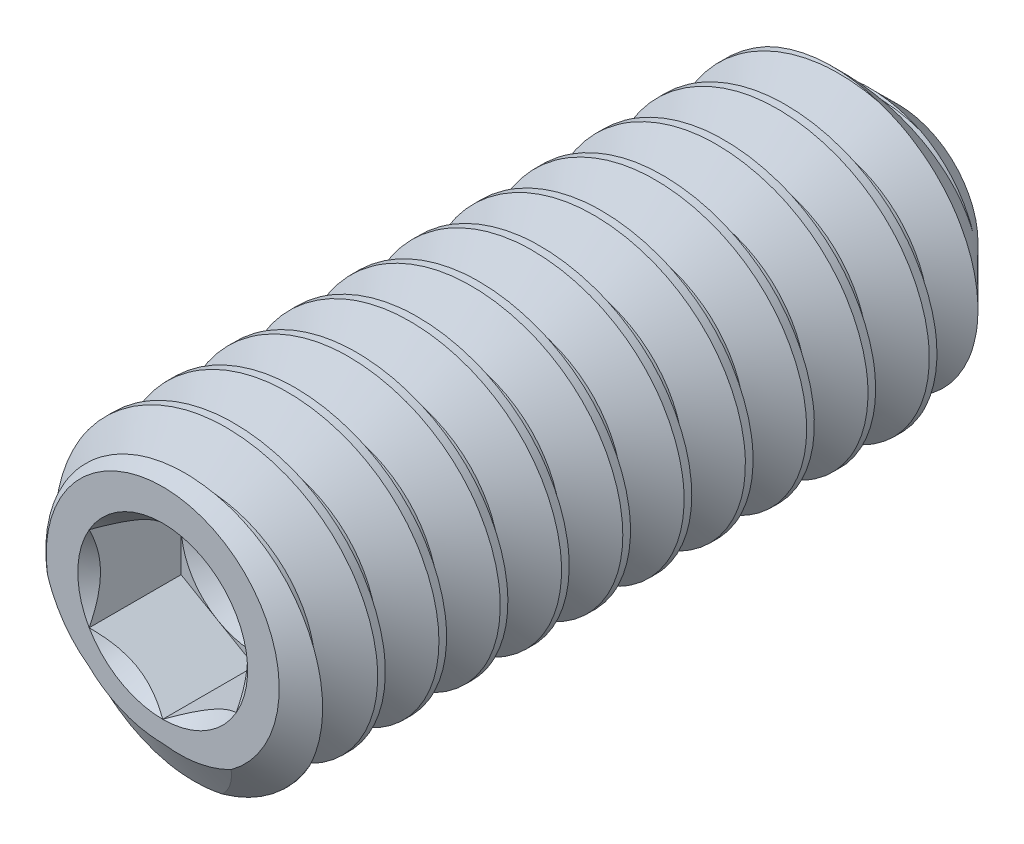
SolidWorks part; units mm, degrees
ref_plane "Front" through (0, 0, 0) normal (0, 0, 1) x (1, 0, 0)
ref_plane "Top" through (0, 0, 0) normal (0, 1, 0) x (1, 0, 0)
ref_plane "Right" through (0, 0, 0) normal (1, 0, 0) x (0, 0, -1)
sketch "Sketch22" plane through (0, 0, 0) normal (1, 0, 0) x (0, 0, -1)
  line L0 (-2.968, 0) -> (-2.968, 1.0058)
  line L1 (-2.968, 1.0058) -> (-2.7919, 1.2573)
  line L2 (-2.7919, 1.2573) -> (2.8136, 1.2573)
  line L3 (2.8136, 1.2573) -> (3.382, 0.689)
  line L4 (3.382, 0.689) -> (2.968, 0)
  line L5 (2.968, 0) -> (-2.968, 0)
  line L6 (2.968, 0) -> (3.382, 0) construction
  line L7 (3.382, 0) -> (3.382, 0.689) construction
  line L8 (3.382, -0.689) -> (2.968, 0) construction
  line L9 (-2.7919, -1.2573) -> (2.8136, -1.2573) construction
  line L10 (3.382, -1.2573) -> (3.382, 1.2573) construction
  line L11 (3.382, 1.2573) -> (2.8528, 1.2573) construction
  point P11 (2.0591, -1.2573)
  point P15 (3.382, 0)
  dimension "D3" = 35
  dimension "D5" = 118
  dimension "D6" = 45
  dimension "D7" = 2.0117
  dimension "D1" = 1.3229
revolve "Revolve1" add sketch "Sketch22" angle 360 about L6
ref_plane "Plane1" through (0, 0, -3.382) normal (0, 0, 1) x (1, 0, 0)
sketch "Sketch27" plane through (0, 0, -3.382) normal (0, 0, 1) x (1, 0, 0)
  circle A0 centre (0, 0) radius 1.2573 construction
  circle A1 centre (0, 0) radius 1.2573
sketch "Sketch23" plane through (0, 0, 2.968) normal (0, 0, 1) x (1, 0, 0)
  line L1 (0, 0.7332) -> (-0.635, 0.3666)
  line L2 (-0.635, 0.3666) -> (-0.635, -0.3666)
  line L3 (-0.635, -0.3666) -> (0, -0.7332)
  line L4 (0, -0.7332) -> (0.635, -0.3666)
  line L5 (0.635, -0.3666) -> (0.635, 0.3666)
  line L6 (0.635, 0.3666) -> (0, 0.7332)
  circle A0 centre (0, 0) radius 0.635 construction
extrude "Cut-Extrude10" cut sketch "Sketch23" against normal blind 0.7937
sketch "Sketch24" plane through (0, 0, 2.968) normal (0, 0, 1) x (1, 0, 0)
  circle A0 centre (0, 0) radius 0.7332
extrude "Cut-Extrude11" cut sketch "Sketch24" against normal through all draft 45
sketch "Sketch26" plane through (0, 0, 2.1743) normal (0, 0, 1) x (1, 0, 0)
  circle A0 centre (0, 0) radius 0.635 construction
  circle A1 centre (0, 0) radius 0.635
extrude "Cut-Extrude12" cut sketch "Sketch26" against normal through all draft 60
sketch "Sketch31" plane through (0, 0, 0) normal (1, 0, 0) x (0, 0, -1)
  line L2 (2.968, 0) -> (3.382, -0.689)
  line L3 (3.382, 0.689) -> (2.968, 0)
ref_axis "Center Axis1" through (0, 0, -42.9554) along (0, 0, 1)
ref_plane "Contact Plane1" through (0, 0, -3.382) normal (0, 0, 1) x (1, 0, 0)
ref_plane "Contact Plane2" through (0, 0, 2.968) normal (0, 0, 1) x (1, 0, 0)
curve "Helix/Spiral1" pitch 0.5292 height 6.8792 radius 1.2573 centre (0, 0, -3.382) axis (0, 0, 1) start towards (0, 1, 0)
sketch "Sketch32" plane through (0, 0, 0) normal (1, 0, 0) x (0, 0, -1)
  line L0 (3.3489, 1.3146) -> (3.8781, 1.3146) construction
  line L1 (3.8781, 1.3146) -> (3.6135, 0.8563) construction
  line L2 (3.6135, 0.8563) -> (3.3489, 1.3146) construction
  line L3 (3.382, 1.2573) -> (2.8528, 1.2573) construction
  line L4 (3.6135, 0.8563) -> (3.6135, 0.9136) construction
  line L5 (3.6135, 1.3146) -> (3.6135, 1.2573) construction
  line L6 (3.5804, 0.9136) -> (3.6466, 0.9136)
  line L7 (3.382, 1.2573) -> (3.845, 1.2573) construction
  line L8 (3.3654, 1.2859) -> (3.8615, 1.2859)
  line L9 (3.3654, 1.2859) -> (3.5804, 0.9136)
  line L10 (3.6466, 0.9136) -> (3.8615, 1.2859)
  point P11 (3.6135, 0.9136)
  point P13 (3.6135, 1.2573)
  point P17 (3.6135, 1.2859)
  dimension "D1" = 0.0661
sweep "Cut-Sweep1" cut profiles "Sketch32" path "Helix/Spiral1"
equation "\"D7@Sketch22\"=\"Dia@Sketch22\"*.8"
equation "\"D3@Helix/Spiral1\"=\"Length@Sketch22\" + \"Pitch@Sketch22\"l1\""
equation "\"hex Depth@Cut-Extrude10\" = \"Hex@Sketch23\" * .625"
equation "\"D1@Sketch22\"=\"Pitch@Sketch22\"*2.5"
equation "\"D4@Helix/Spiral1\"=\"Pitch@Sketch22\""
equation "\"D1@Sketch32\"=\"Pitch@Sketch22\"*.125"
